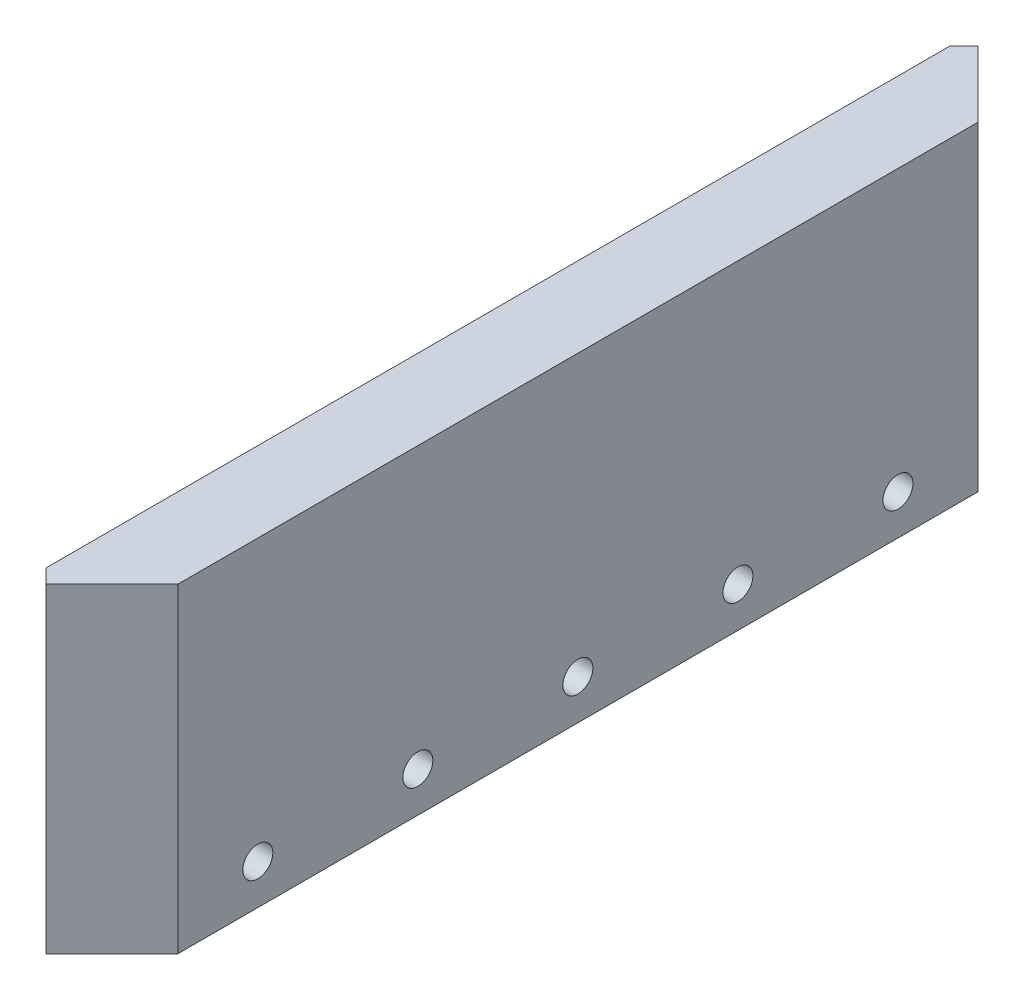
SolidWorks part; units mm, degrees
material "Mahogany"
ref_plane "Front Plane" through (0, 0, 0) normal (0, 0, 1) x (1, 0, 0)
ref_plane "Top Plane" through (0, 0, 0) normal (0, 1, 0) x (1, 0, 0)
ref_plane "Right Plane" through (0, 0, 0) normal (1, 0, 0) x (0, 0, -1)
sketch "Sketch1" plane through (0, 0, 0) normal (1, 0, 0) x (0, 0, -1)
  line L1 (-76.2, 25.4) -> (76.2, 25.4)
  line L2 (-76.2, 25.4) -> (-76.2, -25.4)
  line L3 (-76.2, -25.4) -> (76.2, -25.4)
  line L4 (76.2, 25.4) -> (76.2, -25.4)
  line L5 (-76.2, 25.4) -> (76.2, -25.4) construction
  line L6 (-76.2, -25.4) -> (76.2, 25.4) construction
  point P0 (0, 0)
  dimension "D1" = 152.4
  dimension "D2" = 50.8
extrude "Boss-Extrude1" add sketch "Sketch1" along normal blind 12.7
sketch "Sketch2" plane through (0, 25.4, 0) normal (0, 1, 0) x (1, 0, 0)
  line L0 (0, 76.2) -> (12.7, 63.5)
  line L1 (12.7, 76.2) -> (12.7, -76.2) construction
  line L2 (12.7, 63.5) -> (12.7, 76.2)
  line L3 (12.7, 76.2) -> (0, 76.2)
  line L4 (0, -76.2) -> (12.7, -63.5)
  line L5 (12.7, -63.5) -> (12.7, -76.2)
  line L6 (12.7, -76.2) -> (0, -76.2) construction
  line L7 (12.7, -76.2) -> (0, -76.2)
  point P10 (12.7, -55.3723)
extrude "Cut-Extrude1" cut sketch "Sketch2" against normal through all
sketch "Sketch3" plane through (0, 25.4, 0) normal (0, 1, 0) x (1, 0, 0)
  line L0 (0, 71.7099) -> (2.2451, 73.9549)
  line L1 (0, 76.2) -> (0, -76.2) construction
  line L2 (0, 76.2) -> (12.7, 63.5) construction
  line L3 (2.2451, 73.9549) -> (0, 76.2)
  line L4 (0, 76.2) -> (0, 71.7099)
  line L5 (0, -76.2) -> (0, -71.7099)
  line L6 (0, -71.7099) -> (2.2451, -73.9549)
  line L7 (12.7, -63.5) -> (0, -76.2) construction
  line L8 (2.2451, -73.9549) -> (0, -76.2)
  dimension "D1" = 3.175
extrude "Cut-Extrude2" cut sketch "Sketch3" against normal through all
sketch "Sketch4" plane through (0, 0, 0) normal (-1, 0, 0) x (0, 0, 1)
  line L0 (-76.2, -992.4154) -> (-76.2, 49007.5846) construction
  line L1 (71.7099, -25.4) -> (-71.7099, -25.4) construction
  circle A0 centre (-50.8, -19.05) radius 2.3812
  dimension "D2" = 4.7625
  dimension "D1" = 76.2
  dimension "D3" = 6.35
  dimension "D4" = 25.4
extrude "Cut-Extrude3" cut sketch "Sketch4" against normal through all
pattern_linear "LPattern1" count 5 spacing 25.4 along (0, 0, 1) of "Cut-Extrude3"
